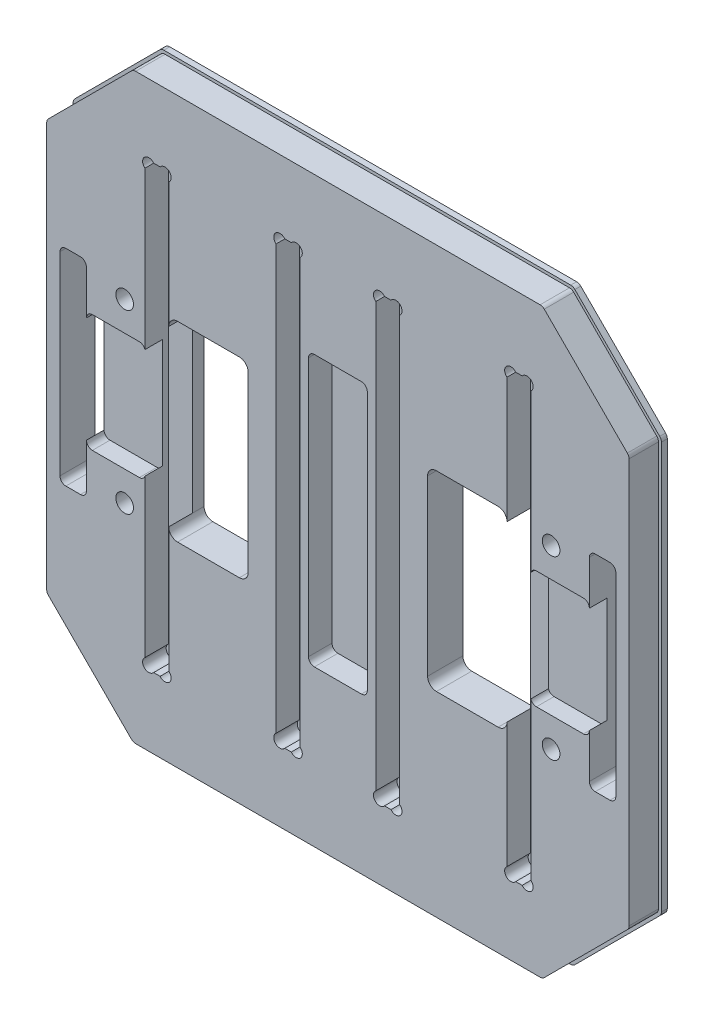
SolidWorks part; units mm, degrees
ref_plane "Front" through (0, 0, 0) normal (0, 0, 1) x (1, 0, 0)
ref_plane "Top" through (0, 0, 0) normal (0, 1, 0) x (1, 0, 0)
ref_plane "Right" through (0, 0, 0) normal (1, 0, 0) x (0, 0, -1)
sketch "Esquisse2" plane through (0, 0, 0) normal (0, 0, 1) x (1, 0, 0)
  line L1 (0, 0) -> (200, 0)
  line L2 (0, 0) -> (0, 200)
  line L3 (0, 200) -> (200, 200)
  line L4 (200, 0) -> (200, 200)
  dimension "D1" = 200
  dimension "D2" = 200
extrude "Boss.-Extru.1" add sketch "Esquisse2" along normal blind 12
sketch "Esquisse3" plane through (0, 0, 12) normal (0, 0, 1) x (1, 0, 0)
  line L0 (0, 100) -> (200, 100) construction
  line L1 (0, 200) -> (0, 0) construction
  line L2 (200, 0) -> (200, 200) construction
  line L3 (0, 0) -> (200, 0) construction
  line L4 (100, 100) -> (100, 198.2097) construction
  line L5 (185.5, 67) -> (185.5, 133)
  line L6 (187.5, 135) -> (192.5, 135)
  line L7 (194.5, 133) -> (194.5, 67)
  line L8 (187.5, 65) -> (192.5, 65)
  line L9 (12.5, 65) -> (7.5, 65)
  line L10 (5.5, 133) -> (5.5, 67)
  line L11 (12.5, 135) -> (7.5, 135)
  line L12 (14.5, 67) -> (14.5, 133)
  line L13 (69.5, 70.5) -> (69.5, 129.5)
  line L14 (66.5, 132.5) -> (45.5, 132.5)
  line L15 (42.5, 129.5) -> (42.5, 70.5)
  line L16 (190, 135) -> (190, 163.9784) construction
  line L17 (190, 163.9784) -> (100, 163.9784) construction
  line L18 (56, 132.5) -> (56, 150.9164) construction
  line L19 (56, 150.9164) -> (100, 150.9164) construction
  line L20 (66.5, 67.5) -> (45.5, 67.5)
  line L21 (133.5, 67.5) -> (154.5, 67.5)
  line L22 (157.5, 129.5) -> (157.5, 70.5)
  line L23 (133.5, 132.5) -> (154.5, 132.5)
  line L24 (130.5, 70.5) -> (130.5, 129.5)
  circle A0 centre (172.5, 130) radius 3
  circle A1 centre (172.5, 70) radius 3
  circle A2 centre (27.5, 70) radius 3
  circle A3 centre (27.5, 130) radius 3
  arc A4 (192.5, 65) -> (194.5, 67) centre (192.5, 67) ccw
  arc A5 (187.5, 65) -> (185.5, 67) centre (187.5, 67) cw
  arc A6 (192.5, 135) -> (194.5, 133) centre (192.5, 133) cw
  arc A7 (185.5, 133) -> (187.5, 135) centre (187.5, 133) cw
  arc A8 (12.5, 65) -> (14.5, 67) centre (12.5, 67) ccw
  arc A9 (7.5, 65) -> (5.5, 67) centre (7.5, 67) cw
  arc A10 (12.5, 135) -> (14.5, 133) centre (12.5, 133) cw
  arc A11 (5.5, 133) -> (7.5, 135) centre (7.5, 133) cw
  arc A12 (133.5, 67.5) -> (130.5, 70.5) centre (133.5, 70.5) cw
  arc A13 (154.5, 67.5) -> (157.5, 70.5) centre (154.5, 70.5) ccw
  arc A14 (157.5, 129.5) -> (154.5, 132.5) centre (154.5, 129.5) ccw
  arc A15 (133.5, 132.5) -> (130.5, 129.5) centre (133.5, 129.5) ccw
  arc A16 (66.5, 67.5) -> (69.5, 70.5) centre (66.5, 70.5) ccw
  arc A17 (45.5, 67.5) -> (42.5, 70.5) centre (45.5, 70.5) cw
  arc A18 (69.5, 129.5) -> (66.5, 132.5) centre (66.5, 129.5) ccw
  arc A19 (45.5, 132.5) -> (42.5, 129.5) centre (45.5, 129.5) ccw
  point P23 (194.5, 100)
  point P24 (185.5, 100)
  point P28 (14.5, 100)
  point P29 (5.5, 100)
  point P41 (42.5, 100)
  point P42 (69.5, 100)
  point P46 (130.5, 100)
  point P47 (157.5, 100)
  point P50 (194.5, 65)
  point P53 (185.5, 65)
  point P56 (194.5, 135)
  point P59 (185.5, 135)
  point P62 (14.5, 65)
  point P65 (5.5, 65)
  point P68 (14.5, 135)
  point P71 (5.5, 135)
  point P74 (130.5, 67.5)
  point P77 (157.5, 67.5)
  point P80 (157.5, 132.5)
  point P83 (130.5, 132.5)
  point P86 (69.5, 67.5)
  point P89 (42.5, 67.5)
  point P92 (69.5, 132.5)
  point P95 (42.5, 132.5)
  dimension "D2" = 60
  dimension "D3" = 44
  dimension "D4" = 6
  dimension "D11" = 2
  dimension "D12" = 3
  dimension "D1" = 100
  dimension "D5" = 9
  dimension "D6" = 13
  dimension "D7" = 70
  dimension "D8" = 90
  dimension "D9" = 65
  dimension "D10" = 27
extrude "Enlèv. mat.-Extru.1" cut sketch "Esquisse3" against normal through all both and the other way through all
chamfer "Chanfrein1" distance 30 distance2 30 4 edges at (0, 200, 6) (200, 200, 6) (200, 0, 6) (0, 0, 6)
sketch "Esquisse4" plane through (0, 0, 12) normal (0, 0, 1) x (1, 0, 0)
  line L16 (169.5858, 199) -> (30.4142, 199)
  line L17 (30.4142, 199) -> (1, 169.5858)
  line L18 (1, 169.5858) -> (1, 30.4142)
  line L19 (1, 30.4142) -> (30.4142, 1)
  line L20 (30.4142, 1) -> (169.5858, 1)
  line L21 (169.5858, 1) -> (199, 30.4142)
  line L22 (199, 30.4142) -> (199, 169.5858)
  line L23 (199, 169.5858) -> (169.5858, 199)
  line L24 (169.5858, 199) -> (30.4142, 199)
  line L25 (30.4142, 199) -> (1, 169.5858)
  line L26 (1, 169.5858) -> (1, 30.4142)
  line L27 (1, 30.4142) -> (30.4142, 1)
  line L28 (30.4142, 1) -> (169.5858, 1)
  line L29 (169.5858, 1) -> (199, 30.4142)
  line L30 (199, 30.4142) -> (199, 169.5858)
  line L31 (199, 169.5858) -> (169.5858, 199)
  line L32 (170, 200) -> (30, 200)
  line L33 (30, 200) -> (0, 170)
  line L34 (0, 170) -> (0, 30)
  line L35 (0, 30) -> (30, 0)
  line L36 (30, 0) -> (170, 0)
  line L37 (170, 0) -> (200, 30)
  line L38 (200, 30) -> (200, 170)
  line L39 (200, 170) -> (170, 200)
  line L40 (170, 200) -> (30, 200)
  line L41 (30, 200) -> (0, 170)
  line L42 (0, 170) -> (0, 30)
  line L43 (0, 30) -> (30, 0)
  line L44 (30, 0) -> (170, 0)
  line L45 (170, 0) -> (200, 30)
  line L46 (200, 30) -> (200, 170)
  line L47 (200, 170) -> (170, 200)
  dimension "D1" = 1
  dimension "D2" = 0
extrude "Enlèv. mat.-Extru.2" cut sketch "Esquisse4" against normal blind 10
sketch "Esquisse5" plane through (0, 0, 12) normal (0, 0, 1) x (1, 0, 0)
  line L0 (100, 0) -> (100, 100) construction
  line L1 (167.5, 120) -> (183.5, 120)
  line L2 (165.5, 118) -> (165.5, 82)
  line L3 (167.5, 80) -> (183.5, 80)
  line L4 (185.5, 118) -> (185.5, 82)
  line L5 (30, 0) -> (170, 0) construction
  line L6 (100, 100) -> (165.5, 100) construction
  line L8 (100, 100) -> (69.5, 100) construction
  line L9 (69.5, 70.5) -> (69.5, 129.5) construction
  line L10 (14.5, 118) -> (14.5, 82)
  line L11 (32.5, 80) -> (16.5, 80)
  line L12 (34.5, 118) -> (34.5, 82)
  line L13 (32.5, 120) -> (16.5, 120)
  arc A0 (165.5, 82) -> (167.5, 80) centre (167.5, 82) ccw
  arc A1 (183.5, 80) -> (185.5, 82) centre (183.5, 82) ccw
  arc A2 (183.5, 120) -> (185.5, 118) centre (183.5, 118) cw
  arc A3 (167.5, 120) -> (165.5, 118) centre (167.5, 118) ccw
  arc A4 (32.5, 120) -> (34.5, 118) centre (32.5, 118) cw
  arc A5 (16.5, 120) -> (14.5, 118) centre (16.5, 118) ccw
  arc A6 (16.5, 80) -> (14.5, 82) centre (16.5, 82) cw
  arc A7 (34.5, 82) -> (32.5, 80) centre (32.5, 82) cw
  point P14 (165.5, 80)
  point P17 (185.5, 80)
  point P22 (165.5, 120)
  point P35 (34.5, 120)
  point P36 (14.5, 80)
  point P37 (34.5, 80)
  dimension "D4" = 2
  dimension "D1" = 20
  dimension "D2" = 65.5
  dimension "D3" = 40
extrude "Enlèv. mat.-Extru.3" cut sketch "Esquisse5" against normal blind 6
sketch "Esquisse6" plane through (0, 0, 12) normal (0, 0, 1) x (1, 0, 0)
  line L0 (69.5, 100) -> (130.5, 100) construction
  line L1 (157.5, 175) -> (165.6, 175)
  line L2 (157.5, 175) -> (157.5, 25)
  line L3 (157.5, 25) -> (165.6, 25)
  line L4 (165.6, 175) -> (165.6, 25)
  line L5 (69.5, 70.5) -> (69.5, 129.5) construction
  line L6 (130.5, 129.5) -> (130.5, 70.5) construction
  line L7 (100, 100) -> (100, 191.362) construction
  line L8 (130.5, 100) -> (157.5, 100) construction
  line L9 (157.5, 70.5) -> (157.5, 129.5) construction
  line L10 (34.4, 175) -> (34.4, 25)
  line L11 (42.5, 25) -> (34.4, 25)
  line L12 (42.5, 175) -> (42.5, 25)
  line L13 (42.5, 175) -> (34.4, 175)
  line L14 (112.9, 100) -> (100, 100) construction
  line L15 (112.9, 175) -> (121, 175)
  line L16 (112.9, 175) -> (112.9, 25)
  line L17 (112.9, 25) -> (121, 25)
  line L18 (121, 175) -> (121, 25)
  line L19 (79, 175) -> (79, 25)
  line L20 (87.1, 25) -> (79, 25)
  line L21 (87.1, 175) -> (87.1, 25)
  line L22 (87.1, 175) -> (79, 175)
  dimension "D1" = 150
  dimension "D2" = 8.1
  dimension "D3" = 8.1
  dimension "D4" = 150
  dimension "D5" = 21
extrude "Enlèv. mat.-Extru.4" cut sketch "Esquisse6" against normal blind 8
sketch "Esquisse7" plane through (0, 0, 12) normal (0, 0, 1) x (1, 0, 0)
  line L0 (87.1, 100) -> (112.9, 100) construction
  line L1 (87.1, 25) -> (87.1, 175) construction
  line L2 (112.9, 175) -> (112.9, 25) construction
  line L3 (100, 100) -> (100, 199) construction
  line L4 (169.5858, 199) -> (30.4142, 199) construction
  line L5 (114.2, 173.7) -> (112.9, 175) construction
  line L6 (121, 175) -> (112.9, 175) construction
  line L7 (116.95, 175) -> (116.95, 100) construction
  line L8 (121, 175) -> (112.9, 175) construction
  line L9 (116.95, 100) -> (112.9, 100) construction
  line L10 (119.7, 173.7) -> (121, 175) construction
  line L11 (119.7, 26.3) -> (121, 25) construction
  line L12 (114.2, 26.3) -> (112.9, 25) construction
  line L13 (116.95, 100) -> (139.25, 100) construction
  line L14 (139.25, 100) -> (139.25, 192.3771) construction
  line L15 (164.3, 26.3) -> (165.6, 25) construction
  line L16 (158.8, 26.3) -> (157.5, 25) construction
  line L17 (158.8, 173.7) -> (157.5, 175) construction
  line L18 (161.55, 100) -> (165.6, 100) construction
  line L19 (161.55, 175) -> (161.55, 100) construction
  line L20 (164.3, 173.7) -> (165.6, 175) construction
  line L21 (165.6, 175) -> (157.5, 175) construction
  line L22 (35.7, 173.7) -> (34.4, 175) construction
  line L23 (38.45, 175) -> (38.45, 100) construction
  line L24 (38.45, 100) -> (34.4, 100) construction
  line L25 (41.2, 173.7) -> (42.5, 175) construction
  line L26 (41.2, 26.3) -> (42.5, 25) construction
  line L27 (35.7, 26.3) -> (34.4, 25) construction
  line L28 (60.75, 100) -> (60.75, 192.3771) construction
  line L29 (83.05, 100) -> (60.75, 100) construction
  line L30 (85.8, 26.3) -> (87.1, 25) construction
  line L31 (80.3, 26.3) -> (79, 25) construction
  line L32 (80.3, 173.7) -> (79, 175) construction
  line L33 (83.05, 100) -> (87.1, 100) construction
  line L34 (83.05, 175) -> (83.05, 100) construction
  line L35 (85.8, 173.7) -> (87.1, 175) construction
  circle A0 centre (114.2, 173.7) radius 2.1
  circle A1 centre (119.7, 173.7) radius 2.1
  circle A2 centre (119.7, 26.3) radius 2.1
  circle A3 centre (114.2, 26.3) radius 2.1
  circle A4 centre (164.3, 26.3) radius 2.1
  circle A5 centre (158.8, 26.3) radius 2.1
  circle A6 centre (158.8, 173.7) radius 2.1
  circle A7 centre (164.3, 173.7) radius 2.1
  circle A8 centre (35.7, 173.7) radius 2.1
  circle A9 centre (41.2, 173.7) radius 2.1
  circle A10 centre (41.2, 26.3) radius 2.1
  circle A11 centre (35.7, 26.3) radius 2.1
  circle A12 centre (85.8, 26.3) radius 2.1
  circle A13 centre (80.3, 26.3) radius 2.1
  circle A14 centre (80.3, 173.7) radius 2.1
  circle A15 centre (85.8, 173.7) radius 2.1
  point P46 (161.55, 175)
  dimension "D1" = 4.2
  dimension "D2" = 1.3
  dimension "D3" = 1.3
extrude "Enlèv. mat.-Extru.5" cut sketch "Esquisse7" against normal up to vertex (8 mm away) up to point (112.9, 25, 4)
sketch "Esquisse8" plane through (0, 0, 12) normal (0, 0, 1) x (1, 0, 0)
  line L0 (100, 1) -> (100, 199) construction
  line L1 (30.4142, 1) -> (169.5858, 1) construction
  line L2 (169.5858, 199) -> (30.4142, 199) construction
  line L3 (100, 100) -> (252.8445, 100) construction
  line L4 (110, 54) -> (110, 146)
  line L5 (110, 146) -> (90, 146)
  line L6 (90, 54) -> (90, 146)
  line L7 (110, 54) -> (90, 54)
  point P8 (100, 54)
  point P12 (100, 146)
  point P14 (90, 100)
  point P15 (110, 100)
  dimension "D1" = 20
  dimension "D2" = 92
extrude "Enlèv. mat.-Extru.6" cut sketch "Esquisse8" against normal blind 8
fillet "Congé1" radius 2 4 edges at (110, 54, 8) (90, 54, 8) (110, 146, 8) (90, 146, 8)
fillet "Congé2" radius 2 16 edges at (1, 169.5858, 7) (30.4142, 199, 7) (169.5858, 199, 7) (199, 169.5858, 7) (199, 30.4142, 7) (169.5858, 1, 7) (1, 30.4142, 7) (30.4142, 1, 7) (170, 200, 1) (200, 170, 1) (200, 30, 1) (170, 0, 1) (30, 0, 1) (0, 30, 1) (0, 170, 1) (30, 200, 1)
